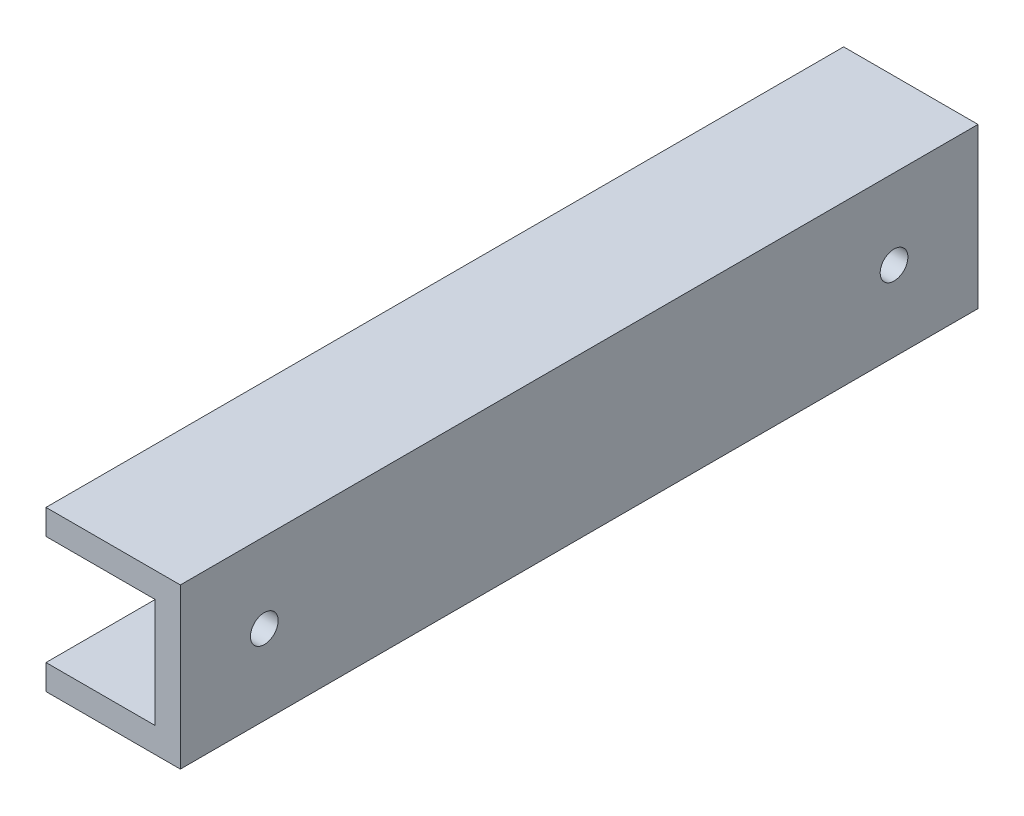
SolidWorks part; units mm, degrees
ref_plane "前视基准面" through (0, 0, 0) normal (0, 0, 1) x (1, 0, 0)
ref_plane "上视基准面" through (0, 0, 0) normal (0, 1, 0) x (1, 0, 0)
ref_plane "右视基准面" through (0, 0, 0) normal (1, 0, 0) x (0, 0, -1)
sketch "草图1" plane through (0, 0, 0) normal (0, 0, 1) x (1, 0, 0)
  line L1 (0, 0) -> (13, 0)
  line L2 (0, 0) -> (0, 13)
  line L3 (0, 13) -> (13, 13)
  line L4 (13, 0) -> (13, 13)
  dimension "D1" = 13
  dimension "D2" = 13
extrude "拉伸-薄壁1" add sketch "草图1" along normal blind 95 thin thin type one direction wall 3
sketch "草图2" plane through (-3, 0, 0) normal (-1, 0, 0) x (0, 0, 1)
  line L0 (0, 16) -> (0, -3) construction
  line L1 (95, 16) -> (95, -3) construction
  circle A0 centre (10, 6.5) radius 1.65
  circle A1 centre (85, 6.5) radius 1.65
  dimension "D1" = 3.3
  dimension "D2" = 3.3
  dimension "D3" = 10
  dimension "D4" = 10
extrude "切除-拉伸1" cut sketch "草图2" against normal blind 30
sketch "草图3" plane through (-3, 0, 0) normal (-1, 0, 0) x (0, 0, 1)
  line L1 (-5.2954, 23.3125) -> (111.6198, 23.3125)
  line L2 (-5.2954, 23.3125) -> (-5.2954, -22.907)
  line L3 (-5.2954, -22.907) -> (111.6198, -22.907)
  line L4 (111.6198, 23.3125) -> (111.6198, -22.907)
extrude "切除-拉伸2" cut sketch "草图3" against normal blind 3
sketch "草图4" plane through (13, 0, 0) normal (-1, 0, 0) x (0, 0, 1)
  line L0 (95, 13) -> (0, 13) construction
  line L1 (23, 13) -> (28, 13)
  line L2 (23, 13) -> (23, 0)
  line L3 (23, 0) -> (28, 0)
  line L4 (28, 13) -> (28, 0)
  line L5 (95, 0) -> (0, 0) construction
  line L6 (95, 13) -> (0, 13) construction
  line L7 (67, 13) -> (72, 13)
  line L8 (67, 13) -> (67, 0)
  line L9 (67, 0) -> (72, 0)
  line L10 (72, 13) -> (72, 0)
  line L11 (95, 0) -> (0, 0) construction
  line L12 (95, 0) -> (95, 13) construction
  line L13 (0, 0) -> (0, 13) construction
  dimension "D1" = 23
  dimension "D2" = 23
  dimension "D3" = 5
  dimension "D4" = 5
extrude "凸台-拉伸1" add sketch "草图4" along normal blind 10
sketch "草图5" plane through (13, 0, 0) normal (-1, 0, 0) x (0, 0, 1)
  line L0 (28, 0) -> (28, 13) construction
  line L1 (28, 9) -> (67, 9)
  line L2 (28, 9) -> (28, 4)
  line L3 (28, 4) -> (67, 4)
  line L4 (67, 9) -> (67, 4)
  line L5 (67, 13) -> (67, 0) construction
  line L6 (67, 0) -> (28, 0) construction
  dimension "D1" = 5
  dimension "D2" = 4
extrude "凸台-拉伸2" add sketch "草图5" along normal blind 10
sketch "草图6" plane through (13, 0, 0) normal (-1, 0, 0) x (0, 0, 1)
  line L1 (23, 13) -> (72, 13)
  line L2 (23, 13) -> (23, 0)
  line L3 (23, 0) -> (72, 0)
  line L4 (72, 13) -> (72, 0)
extrude "凸台-拉伸3" add sketch "草图6" along normal blind 10
sketch "草图7" plane through (3, 0, 0) normal (-1, 0, 0) x (0, 0, 1)
  line L0 (23, 13) -> (23, 0) construction
  line L1 (23, 9) -> (72, 9)
  line L2 (23, 9) -> (23, 4)
  line L3 (23, 4) -> (72, 4)
  line L4 (72, 9) -> (72, 4)
  line L5 (72, 0) -> (72, 13) construction
  line L6 (95, 13) -> (0, 13) construction
  dimension "D1" = 5
  dimension "D2" = 4
extrude "凸台-拉伸4" [suppressed] add sketch "草图7" along normal blind 3
sketch "草图8" plane through (3, 0, 0) normal (-1, 0, 0) x (0, 0, 1)
  line L0 (23, 13) -> (23, 0) construction
  line L1 (23, 9) -> (72, 9)
  line L2 (23, 9) -> (23, 4)
  line L3 (23, 4) -> (72, 4)
  line L4 (72, 9) -> (72, 4)
  line L5 (72, 0) -> (72, 13) construction
  line L6 (95, 13) -> (0, 13) construction
  dimension "D1" = 5
  dimension "D2" = 4
extrude "切除-拉伸3" cut sketch "草图8" against normal blind 3
chamfer "倒角1" distance 3 angle 45 2 edges at (6, 6.5, 72) (6, 6.5, 23)
chamfer "倒角2" distance 4 angle 45 2 edges at (13, 6.5, 72) (13, 6.5, 23)
